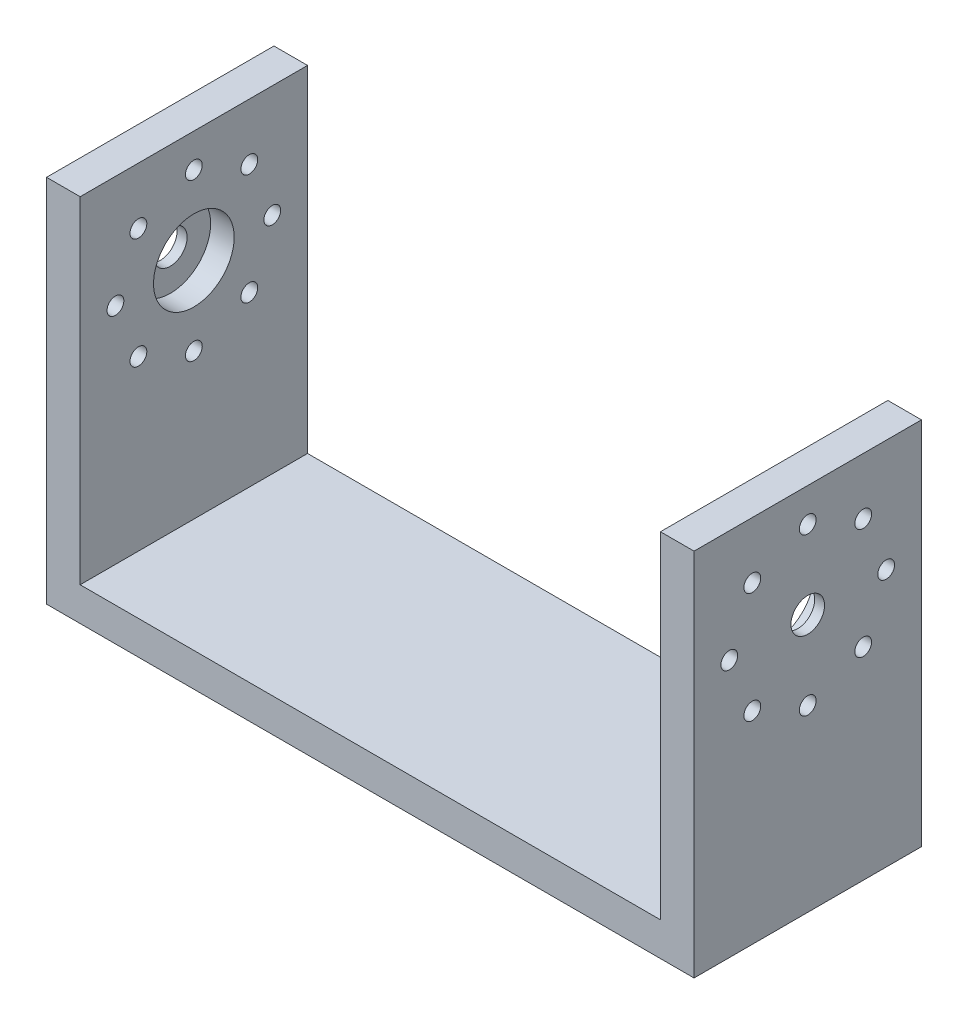
SolidWorks part; units mm, degrees
ref_plane "Front Plane" through (0, 0, 0) normal (0, 0, 1) x (1, 0, 0)
ref_plane "Top Plane" through (0, 0, 0) normal (0, 1, 0) x (1, 0, 0)
ref_plane "Right Plane" through (0, 0, 0) normal (1, 0, 0) x (0, 0, -1)
sketch "Sketch1" plane through (0, 0, 0) normal (0, 1, 0) x (1, 0, 0)
  line L1 (0, 0) -> (57.8, 0)
  line L2 (0, 0) -> (0, 20.3)
  line L3 (0, 20.3) -> (57.8, 20.3)
  line L4 (57.8, 0) -> (57.8, 20.3)
  dimension "D1" = 57.8
  dimension "D2" = 20.3
extrude "YawMount" add sketch "Sketch1" along normal blind 3
sketch "Sketch2" plane through (0, 3, 0) normal (0, 1, 0) x (1, 0, 0)
  line L0 (0, 0) -> (57.8, 0) construction
  line L1 (0, 20.3) -> (3, 20.3)
  line L2 (0, 20.3) -> (0, 0)
  line L3 (0, 0) -> (3, 0)
  line L4 (3, 20.3) -> (3, 0)
  line L6 (57.8, 20.3) -> (54.8, 20.3)
  line L7 (57.8, 20.3) -> (57.8, 0)
  line L8 (57.8, 0) -> (54.8, 0)
  line L9 (54.8, 20.3) -> (54.8, 0)
  dimension "D1" = 3
  dimension "D2" = 3
extrude "BodyConnectors" add sketch "Sketch2" along normal blind 30
sketch "Sketch3" plane through (57.8, 0, 0) normal (1, 0, 0) x (0, 0, -1)
  line L0 (0, 33) -> (20.3, 33) construction
  circle A0 centre (10.15, 23) radius 1.5
  circle A1 centre (17.15, 23) radius 0.75
  circle A2 centre (15.0997, 18.0503) radius 0.75
  circle A3 centre (10.15, 16) radius 0.75
  circle A4 centre (5.2003, 18.0503) radius 0.75
  circle A5 centre (3.15, 23) radius 0.75
  circle A6 centre (5.2003, 27.9497) radius 0.75
  circle A7 centre (10.15, 30) radius 0.75
  circle A8 centre (15.0997, 27.9497) radius 0.75
  point P4 (10.15, 33)
  point P24 (10.15, 23)
  dimension "D1" = 3
  dimension "D2" = 1.5
  dimension "D3" = 20
  dimension "D4" = 7
  dimension "D5" = 8
extrude "Axle-Mounts" cut sketch "Sketch3" against normal up to surface (57.8 mm away) up to face at (0, 16.5, -10.15)
sketch "Sketch4" plane through (54.8, 0, 0) normal (-1, 0, 0) x (0, 0, 1)
  circle A0 centre (-10.15, 23) radius 3.6
  circle A1 centre (-10.15, 23) radius 1.5 construction
  dimension "D1" = 7.2
extrude "Slide-Counterbore" cut sketch "Sketch4" against normal blind 2.12
sketch "Sketch5" plane through (3, 0, 0) normal (1, 0, 0) x (0, 0, -1)
  circle A0 centre (10.15, 23) radius 3.6
  circle A1 centre (10.15, 23) radius 1.5 construction
  dimension "D1" = 7.2
extrude "Gear-Counterbore" cut sketch "Sketch5" against normal blind 2.1
equation "\"srv_w\"= 40.43mm'width of Sain Smart SR319"
equation "\"D1@Sketch1\"=51.8mm + \"mnt_thick\"*2"
equation "\"srv_h\"= 40.61mm'height of Sain Smart SR319"
equation "\"srv_d\"= 20.3mm'depth of Sain Smart SR319"
equation "\"D2@Sketch1\"=\"srv_d\""
equation "\"mnt_thick\"= 3mm'thickness of bracket"
equation "\"D1@YawMount\" = \"mnt_thick\""
equation "\"D2@Sketch2\"=\"mnt_thick\""
equation "\"D1@Sketch2\"=\"mnt_thick\""
